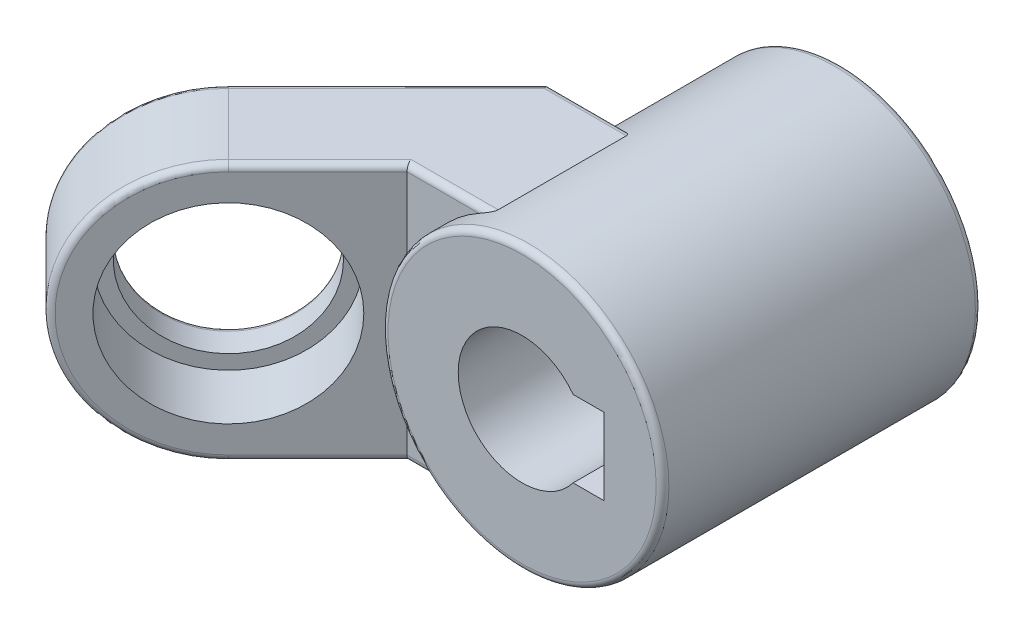
SolidWorks part; units mm, degrees
ref_plane "Front Plane" through (0, 0, 0) normal (0, 0, 1) x (1, 0, 0)
ref_plane "Top Plane" through (0, 0, 0) normal (0, 1, 0) x (1, 0, 0)
ref_plane "Right Plane" through (0, 0, 0) normal (1, 0, 0) x (0, 0, -1)
sketch "Esquisse1" plane through (0, 0, 0) normal (0, 0, 1) x (1, 0, 0)
  circle A0 centre (0, 0) radius 22
  dimension "D1" = 44
extrude "Boss.-Extru.1" add sketch "Esquisse1" along normal blind 50
sketch "Esquisse2" plane through (0, 0, 50) normal (0, 0, 1) x (1, 0, 0)
  line L0 (-22, 0) -> (22, 0) construction
  circle A0 centre (0, 0) radius 22 construction
ref_plane "Plan1" through (0, 0, 0) normal (0, -1, 0) x (1, 0, 0)
sketch "Esquisse3" plane through (0, 0, 0) normal (0, -1, 0) x (1, 0, 0)
  line L0 (0, 0) -> (0, 96) construction
  line L1 (0, 96) -> (-35.9917, 60.0083) construction
  dimension "D1" = 96
  dimension "D2" = 45
  dimension "D3" = 50.9
sketch "Esquisse4" plane through (0, 0, 0) normal (0, -1, 0) x (1, 0, 0)
  line L0 (-35.9917, 60.0083) -> (-50.2753, 74.2918)
  line L1 (-50.2753, 74.2918) -> (-61.3062, 63.261)
  line L2 (-61.3062, 63.261) -> (-22, 23.9548)
  line L3 (-22, 50) -> (-22, 0) construction
  line L4 (-35.9917, 60.0083) -> (-22, 46.0165)
  line L5 (-22, 23.9548) -> (0, 23.9548)
  line L6 (0, 23.9548) -> (0, 46.0165)
  line L7 (0, 0) -> (0, 96) construction
  line L8 (0, 46.0165) -> (-22, 46.0165)
  line L9 (0, 96) -> (-35.9917, 60.0083) construction
  point P3 (0, 0)
  point P13 (0, 0)
  point P14 (0, 0)
  dimension "D1" = 20.2
  dimension "D2" = 15.6
  dimension "D3" = 22
extrude "Boss.-Extru.3" add sketch "Esquisse4" along normal blind 20.2 and the other way blind 20.2
sketch "Esquisse5" plane through (0, 0, 0) normal (0, 0, -1) x (-1, 0, 0)
  line L0 (0, 0) -> (-12.8, 0) construction
  line L1 (22, 0) -> (-22, 0) construction
  line L2 (-12.8, -6) -> (-12.8, 6)
  line L3 (-12.8, 6) -> (-8, 6)
  line L4 (-12.8, -6) -> (-8, -6)
  arc A0 (-8, -6) -> (-8, 6) centre (0, 0) ccw
  dimension "D1" = 20
  dimension "D2" = 12.8
  dimension "D3" = 6
extrude "Enlèv. mat.-Extru.1" cut sketch "Esquisse5" against normal up to next
sketch "Esquisse6" plane through (12.0083, 0, 12.0083) normal (0.7071, 0, 0.7071) x (0.7071, 0, -0.7071)
  line L0 (-88.0823, 0) -> (-67.8823, 0) construction
  line L1 (-88.0823, 20.2) -> (-88.0823, -20.2) construction
  circle A0 centre (-67.8823, 0) radius 15
  dimension "D2" = 30
  dimension "D1" = 20.2
extrude "Enlèv. mat.-Extru.2" cut sketch "Esquisse6" against normal blind 10.3
sketch "Esquisse7" plane through (4.7251, 0, 4.7251) normal (0.7071, 0, 0.7071) x (0.7071, 0, -0.7071)
  circle A0 centre (-67.8823, 0) radius 15 construction
  circle A1 centre (-67.8823, 0) radius 15 construction
  circle A2 centre (-67.8823, 0) radius 12.75
  dimension "D1" = 25.5
extrude "Enlèv. mat.-Extru.3" cut sketch "Esquisse7" against normal up to next
fillet "Congé1" radius 1 1 edges at (-56.0382, 0, 57.993)
sketch "Esquisse8" plane through (0, 0, 0) normal (0, 0, -1) x (-1, 0, 0)
  circle A0 centre (0, 0) radius 18
  dimension "D1" = 36
extrude "Enlèv. mat.-Extru.4" cut sketch "Esquisse8" against normal blind 2
sketch "Esquisse10" plane through (12.0083, 0, 12.0083) normal (0.7071, 0, 0.7071) x (0.7071, 0, -0.7071)
  line L1 (-48.0949, 20.2) -> (-88.0823, 20.2) construction
  line L2 (0, 0) -> (-67.8823, 0) construction
  line L3 (0, 0) -> (-67.8823, 0) construction
  line L4 (-67.8823, 20.2) -> (-92.8823, 20.2)
  line L5 (-92.8823, 20.2) -> (-92.8823, -20.2)
  line L6 (-92.8823, -20.2) -> (-67.8823, -20.2)
  arc A0 (-67.8823, -20.2) -> (-67.8823, 20.2) centre (-67.8823, 0) cw
  point P1 (0, 0)
  point P13 (0, 0)
  point P14 (-93.6372, 20.2)
  dimension "D1" = 20.2
  dimension "D2" = 25
extrude "Enlèv. mat.-Extru.5" cut sketch "Esquisse10" against normal up to next (15.6 mm away)
fillet "Congé5" radius 1 12 edges at (-34.5113, -20.2, 36.4661) (-61.3062, 0, 63.261) (-28.9959, 20.2, 53.0124) (-50.2753, 0, 74.2918) (-15.3578, -20.2, 23.9548) (-15.3578, 20.2, 23.9548) (-34.5113, 20.2, 36.4661) (-15.3578, 20.2, 46.0165) (-15.3578, -20.2, 46.0165) (-28.9959, -20.2, 53.0124) (22, 0, 0) (22, 0, 50)
